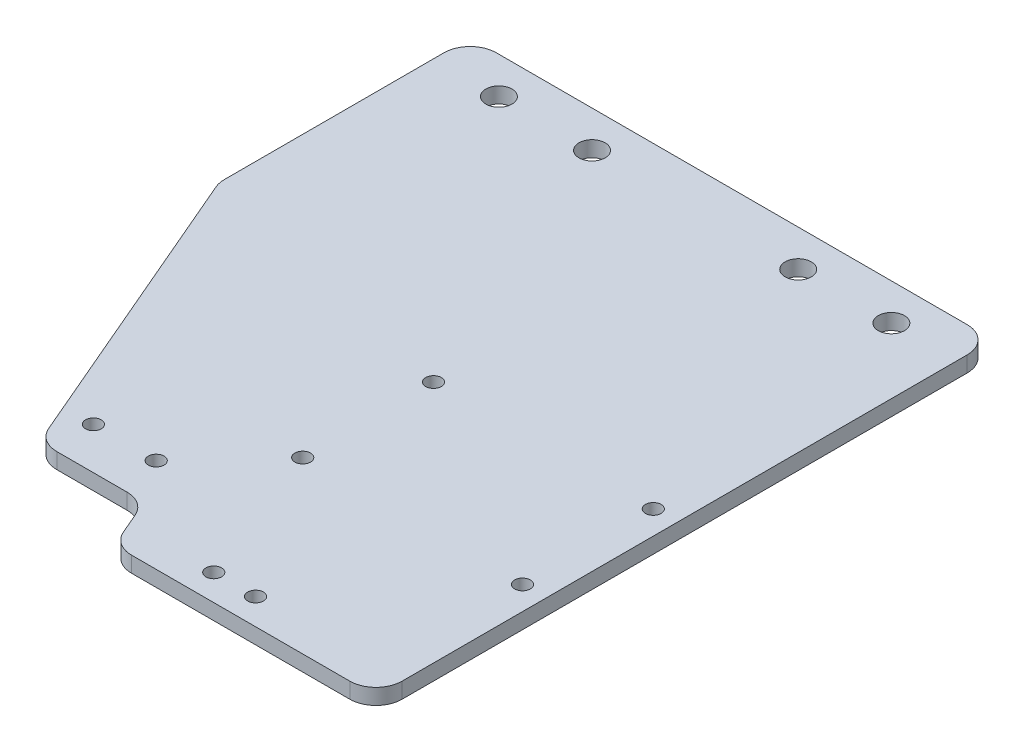
SolidWorks part; units mm, degrees
material "Hexcel AS4C (3000 丝)"
ref_plane "前视基准面" through (0, 0, 0) normal (0, 0, 1) x (1, 0, 0)
ref_plane "上视基准面" through (0, 0, 0) normal (0, 1, 0) x (1, 0, 0)
ref_plane "右视基准面" through (0, 0, 0) normal (1, 0, 0) x (0, 0, -1)
sketch "草图1" plane through (0, 0, 0) normal (0, 1, 0) x (1, 0, 0)
  line L1 (-50, 59) -> (50, 59)
  line L2 (-50, 59) -> (-50, -59)
  line L3 (-50, -59) -> (50, -59)
  line L4 (50, 59) -> (50, -59)
  line L5 (-50, 59) -> (50, -59) construction
  line L6 (-50, -59) -> (50, 59) construction
  point P0 (0, 0)
  dimension "D1" = 100
  dimension "D2" = 118
extrude "凸台-拉伸1" add sketch "草图1" along normal blind 3
sketch "草图3" plane through (0, 3, 0) normal (0, 1, 0) x (1, 0, 0)
  line L0 (24.5, -14) -> (53.0771, -14) construction
  line L1 (24.5, -14) -> (24.5, -7.291) construction
  line L6 (50, -59) -> (50, 59) construction
  line L7 (3.5, -1.5) -> (45.5, -1.5)
  line L8 (3.5, -1.5) -> (3.5, -26.5)
  line L9 (3.5, -26.5) -> (45.5, -26.5)
  line L10 (45.5, -1.5) -> (45.5, -26.5)
  line L11 (3.5, -1.5) -> (45.5, -26.5) construction
  line L12 (3.5, -26.5) -> (45.5, -1.5) construction
  line L13 (-50, -59) -> (50, -59) construction
  circle A0 centre (3.5, -1.5) radius 1.5
  circle A1 centre (45.5, -1.5) radius 1.5
  circle A2 centre (45.5, -26.5) radius 1.5
  circle A3 centre (3.5, -26.5) radius 1.5
  point P13 (24.5, -14)
  dimension "D3" = 3
  dimension "D1" = 42
  dimension "D2" = 25
  dimension "D4" = 25.5
  dimension "D5" = 45
extrude "切除-拉伸2" cut sketch "草图3" against normal blind 3 contours A0 | A1 | A2 | A3
sketch "草图4" plane through (0, 3, 0) normal (0, 1, 0) x (1, 0, 0)
  line L0 (28.6, 54.281) -> (28.6, 42.6782) construction
  line L1 (50, -59) -> (50, 59) construction
  line L2 (50, 59) -> (-50, 59) construction
  line L3 (0, 0) -> (0, 26.4467) construction
  circle A0 centre (37.5, 52) radius 2.5
  circle A1 centre (19.7, 52) radius 2.5
  circle A2 centre (-19.7, 52) radius 2.5
  circle A3 centre (-37.5, 52) radius 2.5
  dimension "D2" = 5
  dimension "D1" = 21.4
  dimension "D3" = 17.8
  dimension "D4" = 7
extrude "切除-拉伸3" cut sketch "草图4" against normal blind 3
sketch "草图5" plane through (0, 3, 0) normal (0, 1, 0) x (1, 0, 0)
  line L0 (18, -42.6608) -> (18, -55.2812) construction
  line L1 (50, -59) -> (50, 59) construction
  line L2 (-50, -59) -> (50, -59) construction
  circle A0 centre (22, -54) radius 1.5
  circle A1 centre (14, -54) radius 1.5
  dimension "D2" = 3
  dimension "D1" = 32
  dimension "D3" = 8
  dimension "D4" = 5
extrude "切除-拉伸4" cut sketch "草图5" against normal blind 3
sketch "草图7" plane through (0, 3, 0) normal (0, 1, 0) x (1, 0, 0)
  line L0 (-50, 11) -> (-50, -59)
  line L1 (-50, 59) -> (-50, -59) construction
  line L2 (-50, -59) -> (-20, -59)
  line L3 (-50, -59) -> (50, -59) construction
  line L4 (-20, -59) -> (-50, 11)
  line L5 (-24.2857, -49) -> (-4.2857, -49)
  line L6 (-4.2857, -49) -> (0, -59)
  line L7 (-20, -59) -> (0, -59)
  line M8 (-50, 59) -> (-50, -59)
  line M9 (-50, -59) -> (50, -59)
  dimension "D1" = 70
  dimension "D2" = 30
  dimension "D3" = 10
  dimension "D4" = 20
extrude "切除-拉伸6" cut sketch "草图7" against normal blind 3 contours L4 M9 M8 | L6 L5 L4 M9 region at (-40, 3, 35.6667) region at (-12.1429, 3, 54)
sketch "草图9" plane through (0, 3, 0) normal (0, 1, 0) x (1, 0, 0)
  line L0 (-16, -38.1262) -> (-16, -46.1648) construction
  line L1 (50, -59) -> (50, 59) construction
  line L2 (0, -59) -> (50, -59) construction
  circle A0 centre (-22, -41) radius 1.5
  circle A1 centre (-10, -41) radius 1.5
  dimension "D1" = 3
  dimension "D2" = 12
  dimension "D3" = 66
  dimension "D4" = 18
extrude "切除-拉伸8" cut sketch "草图9" against normal blind 10
fillet "圆角3" radius 5 7 edges at (-50, 1.5, -59) (-50, 1.5, -11) (-24.2857, 1.5, 49) (-4.2857, 1.5, 49) (0, 1.5, 59) (50, 1.5, 59) (50, 1.5, -59)
sketch "草图10" plane through (0, 3, 0) normal (0, 1, 0) x (1, 0, 0)
  line L1 (3.5, -1.5) -> (45.5, -26.5) construction
  line L2 (45.5, -26.5) -> (45.5, -1.5) construction
  line L3 (45.5, -1.5) -> (3.5, -26.5) construction
  circle A5 centre (24.5, -14) radius 12.5
  dimension "D1" = 25
extrude "切除-拉伸9" [suppressed] cut sketch "草图10" against normal blind 10 contours A5
sketch "草图11" plane through (0, 0, 0) normal (0, -1, 0) x (1, 0, 0)
  circle A0 centre (-37.7502, -37.1316) radius 5
  circle A1 centre (-22.7502, -37.1316) radius 5
  circle A2 centre (-7.7502, -37.1316) radius 5
  circle A3 centre (7.2498, -37.1316) radius 5
  circle A4 centre (22.2498, -37.1316) radius 5
  circle A5 centre (37.2498, -37.1316) radius 5
  circle A6 centre (-37.7502, -22.1316) radius 5
  circle A7 centre (-22.7502, -22.1316) radius 5
  circle A8 centre (-7.7502, -22.1316) radius 5
  circle A9 centre (7.2498, -22.1316) radius 5
  circle A10 centre (22.2498, -22.1316) radius 5
  circle A11 centre (37.2498, -22.1316) radius 5
  dimension "D1" = 10
  dimension "D2" = 6
  dimension "D3" = 2
extrude "切除-拉伸10" [suppressed] cut sketch "草图11" against normal blind 10
sketch "草图12" plane through (0, 3, 0) normal (0, 1, 0) x (1, 0, 0)
  line L0 (45, 59) -> (-45, 59) construction
  line L1 (28, 59) -> (33, 59)
  line L2 (28, 59) -> (28, -59)
  line L3 (28, -59) -> (33, -59)
  line L4 (33, 59) -> (33, -59)
  line L5 (3.297, -59) -> (45, -59) construction
  line L6 (50, -54) -> (50, 54) construction
  dimension "D1" = 5
  dimension "D2" = 17
extrude "凸台-拉伸2" [suppressed] add sketch "草图12" along normal blind 2
sketch "草图13" [suppressed] plane through (33, 0, 0) normal (1, 0, 0) x (0, 0, -1)
  line L0 (-59, 3) -> (-36, 5)
  line L1 (-59, 5) -> (59, 5) construction
  line L2 (59, 3) -> (39, 5)
  line L3 (59, 5) -> (59, 3) construction
  line L4 (-36, 5) -> (-59, 5)
  line L5 (-59, 5) -> (-59, 3)
  line L6 (39, 5) -> (59, 5)
  line L7 (59, 5) -> (59, 3)
  dimension "D1" = 75
  dimension "D2" = 20
extrude "切除-拉伸11" [suppressed] cut sketch "草图13" against normal blind 10
sketch "草图14" plane through (0, 3, 0) normal (0, 1, 0) x (1, 0, 0)
  circle A0 centre (-32.7013, 35.4241) radius 5
  circle A1 centre (-20.0311, 35.4241) radius 5
  circle A2 centre (-7.3609, 35.4241) radius 5
  circle A3 centre (-20.0311, 17.0484) radius 5
  circle A4 centre (-7.3609, 17.0484) radius 5
  circle A5 centre (-20.0311, -1.3272) radius 5
  circle A6 centre (-7.3609, -1.3272) radius 5
  circle A7 centre (-32.7013, 17.0484) radius 5
  circle A8 centre (-32.7013, -1.3272) radius 5
  dimension "D1" = 10
  dimension "D2" = 3
  dimension "D3" = 3
extrude "切除-拉伸12" [suppressed] cut sketch "草图14" against normal blind 10
sketch "草图15" plane through (0, 0, 0) normal (0, -1, 0) x (1, 0, 0)
  circle A0 centre (-26.011, 15.9664) radius 5
  circle A1 centre (-13.011, 15.9664) radius 5
  circle A2 centre (-19.2026, 29.7457) radius 5
  dimension "D1" = 10
  dimension "D3" = 10
  dimension "D2" = 2
extrude "切除-拉伸13" [suppressed] cut sketch "草图15" against normal blind 10
sketch "草图16" plane through (0, 3, 0) normal (0, 1, 0) x (1, 0, 0)
  circle A0 centre (19.2827, 35.4241) radius 5
  circle A1 centre (19.2827, 17.4241) radius 5
  circle A2 centre (19.2827, -0.5759) radius 5
  circle A3 centre (19.2827, -18.5759) radius 5
  circle A4 centre (19.2827, -36.5759) radius 5
  dimension "D1" = 10
  dimension "D2" = 5
extrude "切除-拉伸14" [suppressed] cut sketch "草图16" against normal blind 10
